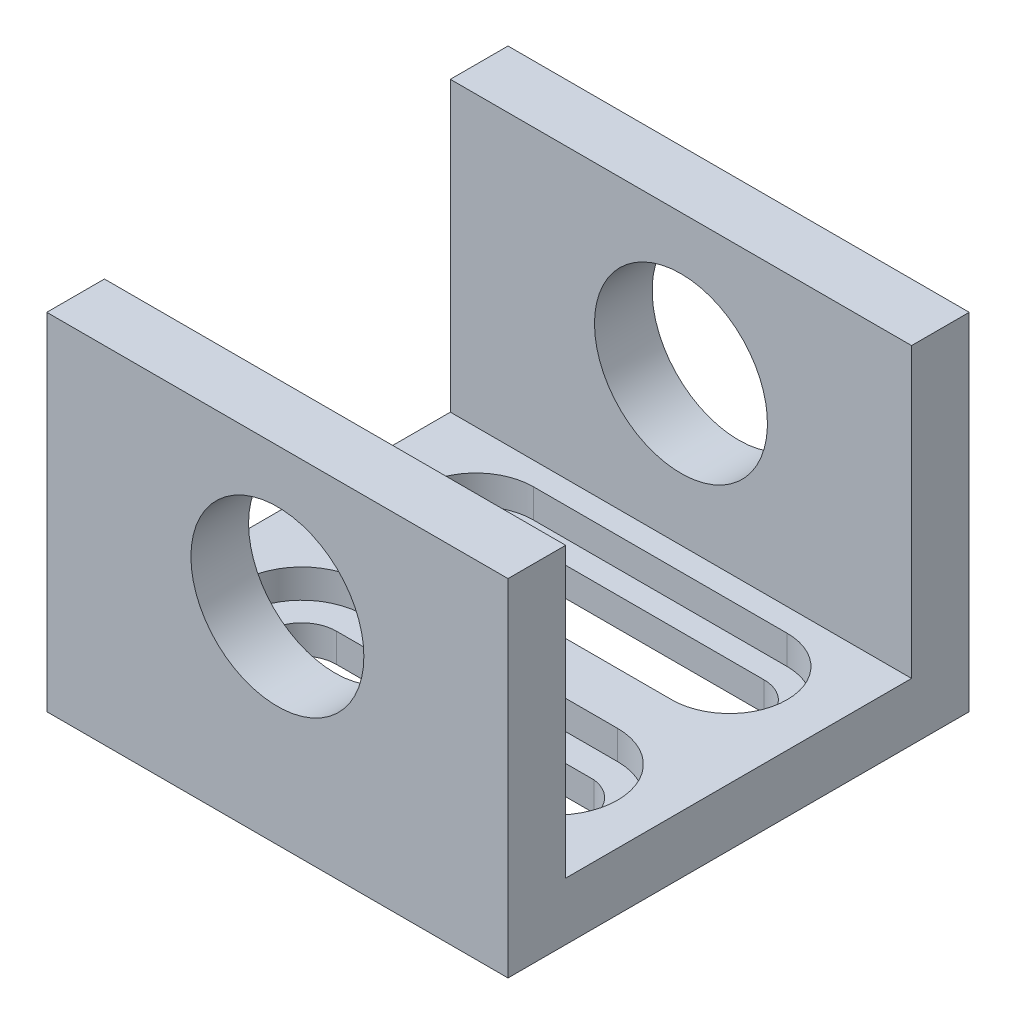
SolidWorks part; units mm, degrees
ref_plane "Front Plane" through (0, 0, 0) normal (0, 0, 1) x (1, 0, 0)
ref_plane "Top Plane" through (0, 0, 0) normal (0, 1, 0) x (1, 0, 0)
ref_plane "Right Plane" through (0, 0, 0) normal (1, 0, 0) x (0, 0, -1)
sketch "Sketch1" plane through (0, 0, 0) normal (1, 0, 0) x (0, 0, -1)
  line L1 (0, 0) -> (-19.05, 0)
  line L3 (0, 3.175) -> (-19.05, 3.175)
  line L5 (3.175, 19.05) -> (0, 19.05)
  line L6 (3.175, 19.05) -> (3.175, 0)
  line L7 (3.175, 0) -> (0, 0)
  line L8 (0, 19.05) -> (0, 3.175)
  line L13 (-19.05, 0) -> (-22.225, 0)
  line L14 (-19.05, 3.175) -> (-19.05, 19.05)
  line L15 (-19.05, 19.05) -> (-22.225, 19.05)
  line L16 (-22.225, 0) -> (-22.225, 19.05)
  dimension "D2" = 3.175
  dimension "D3" = 3.175
  dimension "D4" = 19.05
  dimension "D5" = 19.05
extrude "Boss-Extrude2" add sketch "Sketch1" along normal blind 25.4
sketch "Sketch3" plane through (0, 0, -3.175) normal (0, 0, -1) x (-1, 0, 0)
  line L0 (-25.4, 0) -> (0, 0) construction
  line L2 (0, 0) -> (0, 19.05) construction
  circle A0 centre (-12.7, 11.3665) radius 4.7625
  dimension "D1" = 11.3665
  dimension "D2" = 12.7
extrude "Cut-Extrude1" cut sketch "Sketch3" against normal blind 36.576
sketch "Sketch4" plane through (0, 3.175, 0) normal (0, 1, 0) x (1, 0, 0)
  line L0 (25.4, 3.175) -> (0, 3.175) construction
  line L1 (5.715, -1.27) -> (19.685, -1.27)
  line L3 (5.8455, -2.54) -> (19.8155, -2.54)
  line L5 (5.8455, -6.35) -> (19.8155, -6.35)
  line L7 (5.715, -7.62) -> (19.685, -7.62)
  line L9 (25.4, 0) -> (25.4, -19.05) construction
  line L10 (5.715, -1.27) -> (19.685, -1.27)
  line L11 (19.685, -7.62) -> (5.715, -7.62)
  arc A0 (5.8455, -2.54) -> (5.8455, -6.35) centre (5.8455, -4.445) ccw
  arc A1 (5.715, -1.27) -> (5.715, -7.62) centre (5.715, -4.445) ccw
  arc A2 (19.8155, -2.54) -> (19.8155, -6.35) centre (19.8155, -4.445) cw
  arc A3 (19.685, -1.27) -> (19.685, -7.62) centre (19.685, -4.445) cw
  arc A4 (5.715, -1.27) -> (5.715, -7.62) centre (5.715, -4.445) ccw
  arc A5 (19.685, -1.27) -> (19.685, -7.62) centre (19.685, -4.445) cw
  dimension "D2" = 1.905
  dimension "D3" = 3.175
  dimension "D7" = 5.715
  dimension "D1" = 4.445
  dimension "D4" = 5.715
  dimension "D5" = 9.525
  dimension "D6" = 13.97
extrude "Cut-Extrude2" cut sketch "Sketch4" against normal blind 66.04 contours L3 A2 L5 A0
sketch "Sketch7" plane through (0, 3.175, 0) normal (0, 1, 0) x (1, 0, 0)
  line L1 (5.8455, -2.54) -> (-15.4609, -2.54)
  line L3 (5.8455, -1.27) -> (19.8155, -1.27)
  line L5 (5.8455, -6.35) -> (-15.4609, -6.35)
  line L7 (5.8455, -7.62) -> (19.8155, -7.62)
  arc A0 (5.8455, -1.27) -> (5.8455, -7.62) centre (5.8455, -4.445) ccw
  arc A1 (19.8155, -1.27) -> (19.8155, -7.62) centre (19.8155, -4.445) cw
  dimension "D1" = 1.27
  dimension "D2" = 13.97
  dimension "D3" = 1.27
  dimension "D4" = 13.97
extrude "Cut-Extrude3" cut sketch "Sketch7" against normal blind 1.5875 contours L3 A1 L7 A0
sketch "Sketch8" plane through (0, 3.175, 0) normal (0, 1, 0) x (1, 0, 0)
  line L0 (25.4, -22.225) -> (0, -22.225) construction
  line L1 (5.715, -11.9938) -> (19.901, -11.9938)
  line L3 (5.715, -15.8038) -> (19.4259, -15.8038)
  line L5 (5.9069, -10.4752) -> (19.685, -10.4752)
  line L6 (19.685, -17.3278) -> (5.715, -17.3278)
  line L7 (25.4, 0) -> (25.4, -19.05) construction
  arc A0 (19.4259, -15.8038) -> (19.901, -11.9938) centre (19.685, -13.9015) ccw
  arc A1 (5.715, -11.9938) -> (5.715, -15.8038) centre (5.715, -13.8988) ccw
  arc A3 (5.9069, -10.4752) -> (5.715, -17.3278) centre (5.715, -13.8988) ccw
  arc A5 (19.685, -17.3278) -> (19.685, -10.4752) centre (19.685, -13.9015) ccw
  dimension "D2" = 3.429
  dimension "D6" = 10.2312
  dimension "D7" = 5.715
  dimension "D1" = 1.905
  dimension "D3" = 4.8972
  dimension "D4" = 6.4212
  dimension "D5" = 13.97
extrude "Cut-Extrude4" cut sketch "Sketch8" against normal blind 1.5875 contours L1 A1 L3 A0 | L6 A5 L5 A3 A1 L1 A0 L3 region at (12.7115, 3.175, 13.8992) region at (12.796, 3.175, 10.6945)
extrude "Cut-Extrude5" cut sketch "Sketch8<3>" against normal through all contours L1 A1 L3 A0 region at (12.7115, 3.175, 13.8992)
sketch "Sketch8<3>" plane through (0, 3.175, 0) normal (0, 1, 0) x (1, 0, 0) same geometry as "Sketch8"
